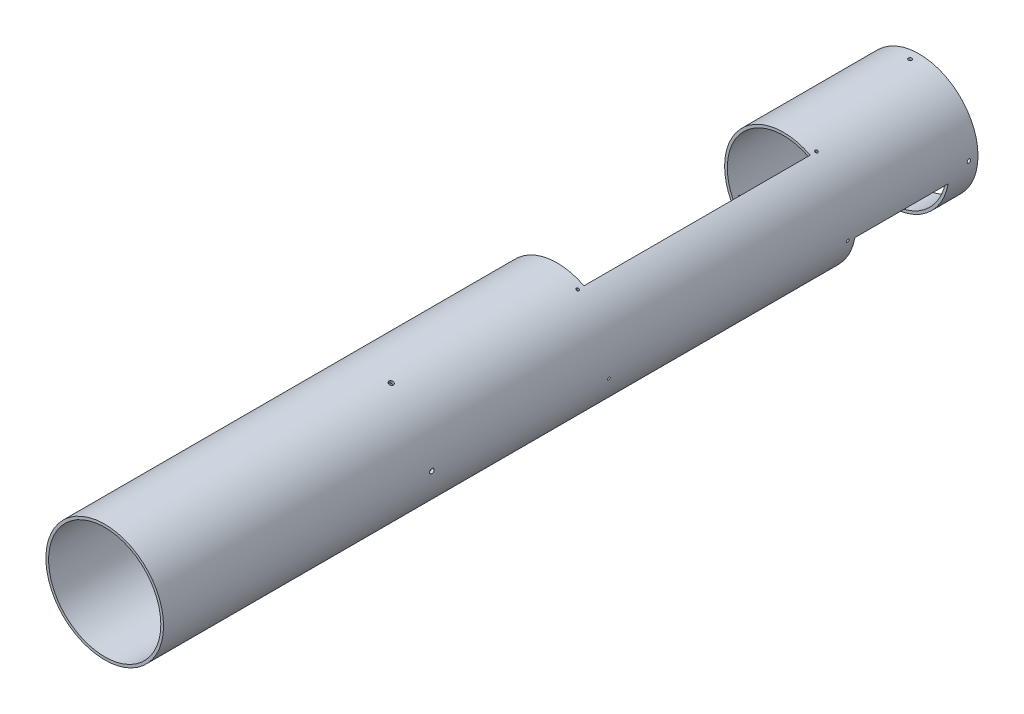
SolidWorks part; units mm, degrees
ref_plane "Front Plane" through (0, 0, 0) normal (0, 0, 1) x (1, 0, 0)
ref_plane "Top Plane" through (0, 0, 0) normal (0, 1, 0) x (1, 0, 0)
ref_plane "Right Plane" through (0, 0, 0) normal (1, 0, 0) x (0, 0, -1)
sketch "Sketch1" plane through (0, 0, 0) normal (0, 0, 1) x (1, 0, 0)
  circle A0 centre (0, 0) radius 62
  circle A1 centre (0, 0) radius 65
  dimension "D1" = 124
  dimension "D2" = 3
extrude "Boss-Extrude1" add sketch "Sketch1" along normal blind 900
sketch "Sketch2" plane through (0, 0, 0) normal (0, 1, 0) x (1, 0, 0)
  line L0 (62, 0) -> (-62, 0) construction
  circle A0 centre (0, -224) radius 1
  circle A1 centre (0, -264) radius 1
  dimension "D1" = 2
  dimension "D3" = 2
  dimension "D2" = 224
  dimension "D4" = 40
ref_plane "Plane1" through (0, 0, 0) normal (-0.7071, 0.7071, 0) x (0.7071, 0.7071, 0)
ref_plane "Plane2" through (-14.1421, 14.1421, 0) normal (-0.7071, 0.7071, 0) x (0.7071, 0.7071, 0)
sketch "Sketch4" plane through (-14.1421, 14.1421, 0) normal (-0.7071, 0.7071, 0) x (0.7071, 0.7071, 0)
  line L0 (-65, 0) -> (-65, -900) construction
  line L1 (-65, -150) -> (65, -150)
  line L2 (-65, -150) -> (-65, -400)
  line L3 (-65, -400) -> (65, -400)
  line L4 (65, -150) -> (65, -400)
  line L5 (65, -900) -> (65, 0) construction
  line L6 (65, 0) -> (-65, 0) construction
  dimension "D1" = 150
  dimension "D2" = 250
extrude "Cut-Extrude4" cut sketch "Sketch4" along normal blind 516
sketch "Sketch5" plane through (0, 0, 0) normal (0, 1, 0) x (1, 0, 0)
  line L0 (-62, 0) -> (62, 0) construction
  circle A0 centre (0, -10) radius 2
  dimension "D1" = 4
  dimension "D2" = 10
extrude "Cut-Extrude5" cut sketch "Sketch5" against normal blind 85
pattern_circular "CirPattern1" count 4 every 90 about axis through (0, 0, 900) along (0, 0, -1) of "Cut-Extrude5"
sketch "Sketch7" plane through (-14.1421, 14.1421, 0) normal (-0.7071, 0.7071, 0) x (0.7071, 0.7071, 0)
  line L0 (-61.8466, -150) -> (61.8466, -150) construction
  line L1 (58.6856, -400) -> (-58.6856, -400) construction
  circle A0 centre (0, -143) radius 1.5
  circle A1 centre (0, -407) radius 1.5
  dimension "D1" = 3
  dimension "D3" = 3
  dimension "D2" = 7
  dimension "D4" = 7
extrude "Cut-Extrude6" cut sketch "Sketch7" along normal blind 243
pattern_circular "CirPattern2" count 5 every 72 about axis through (0, 0, 900) along (0, 0, -1) of "Cut-Extrude6"
sketch "Sketch8" plane through (0, 0, 0) normal (1, 0, 0) x (0, 0, -1)
  line L0 (-900, 65) -> (-900, -65) construction
  circle A0 centre (-603.5, 0) radius 2.5
  dimension "D2" = 5
  dimension "D1" = 296.5
extrude "Cut-Extrude7" cut sketch "Sketch8" along normal blind 209
pattern_circular "CirPattern3" count 5 every 72 about axis through (0, 0, 900) along (0, 0, -1) of "Cut-Extrude7"
ref_plane "Plane3" through (0, 0, 135) normal (0, 0, 1) x (1, 0, 0)
sketch "Sketch9" plane through (0, 0, 135) normal (0, 0, 1) x (1, 0, 0)
  line L0 (-72.0694, 72.0694) -> (72.0694, -72.0694) construction
  line L2 (38.8909, 38.8909) -> (-38.8909, -38.8909) construction
  line L3 (0, 0) -> (11.2871, -64.0125)
  line L4 (1, 0) -> (-1, 0) construction
  line L5 (0, 0) -> (64.0125, -11.2871)
  arc A0 (11.2871, -64.0125) -> (64.0125, -11.2871) centre (0, 0) ccw
  point P6 (0, 0)
  dimension "D1" = 35
extrude "Cut-Extrude8" cut sketch "Sketch9" against normal blind 103
